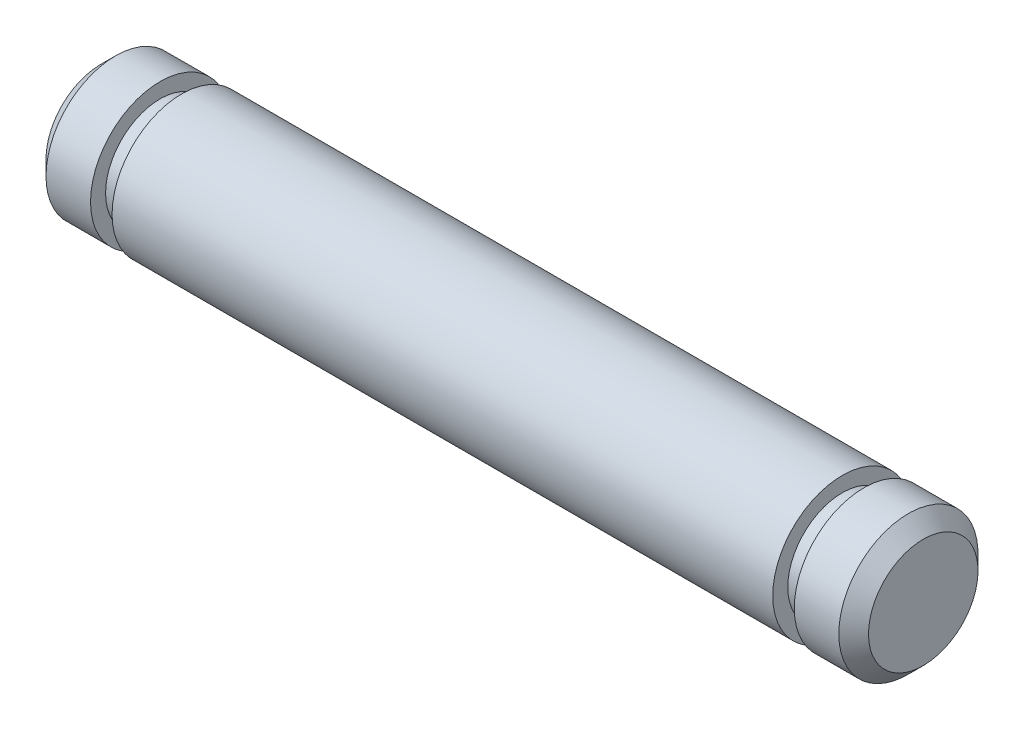
SolidWorks part; units mm, degrees
material "Alloy Steel"
ref_plane "Front" through (0, 0, 0) normal (0, 0, 1) x (1, 0, 0)
ref_plane "Top" through (0, 0, 0) normal (0, 1, 0) x (1, 0, 0)
ref_plane "Right" through (0, 0, 0) normal (1, 0, 0) x (0, 0, -1)
ref_axis "side-side" through (80.9, 0, 0) along (-1, 0, 0)
ref_axis "up-down" through (0, 50, 0) along (0, -1, 0)
ref_axis "front-back" through (0, 0, -80.9) along (0, 0, 1)
sketch "Sketch1" plane through (0, 0, 0) normal (0, 0, 1) x (1, 0, 0)
  line L0 (-17.5799, 0) -> (33.5279, 0) construction
  line L1 (0, -50) -> (0, 50) construction
  line L2 (-7.5946, 0) -> (20.5486, 0)
  line L3 (-7.5946, 0) -> (-7.5946, 2.3813)
  line L4 (-7.5946, 2.3813) -> (-5.5626, 2.3813)
  line L5 (20.5486, 0) -> (20.5486, 2.3813)
  line L6 (20.5486, 0) -> (25.2294, 0) construction
  line L7 (18.5166, 2.3813) -> (18.5166, 1.8669)
  line L8 (18.5166, 1.8669) -> (17.78, 1.8669)
  line L9 (17.78, 2.3813) -> (17.78, 1.8669)
  line L10 (-4.826, 2.3813) -> (17.78, 2.3813)
  line L11 (18.5166, 2.3813) -> (20.5486, 2.3813)
  line L12 (-5.5626, 2.3813) -> (-5.5626, 1.8669)
  line L13 (-5.5626, 1.8669) -> (-4.826, 1.8669)
  line L14 (-4.826, 2.3813) -> (-4.826, 1.8669)
  point P13 (17.78, 2.1241)
  dimension "D1" = 0.7366
  dimension "D2" = 2.032
  dimension "D3" = 4.7625
  dimension "D4" = 3.7338
  dimension "D5" = 17.78
  dimension "D6" = 4.826
revolve "Revolve1" add sketch "Sketch1" angle 360 about L6
chamfer "Chamfer1" distance 0.508 angle 45 2 edges at (-7.5946, 0, 2.3813) (20.5486, 0, 2.3813)
